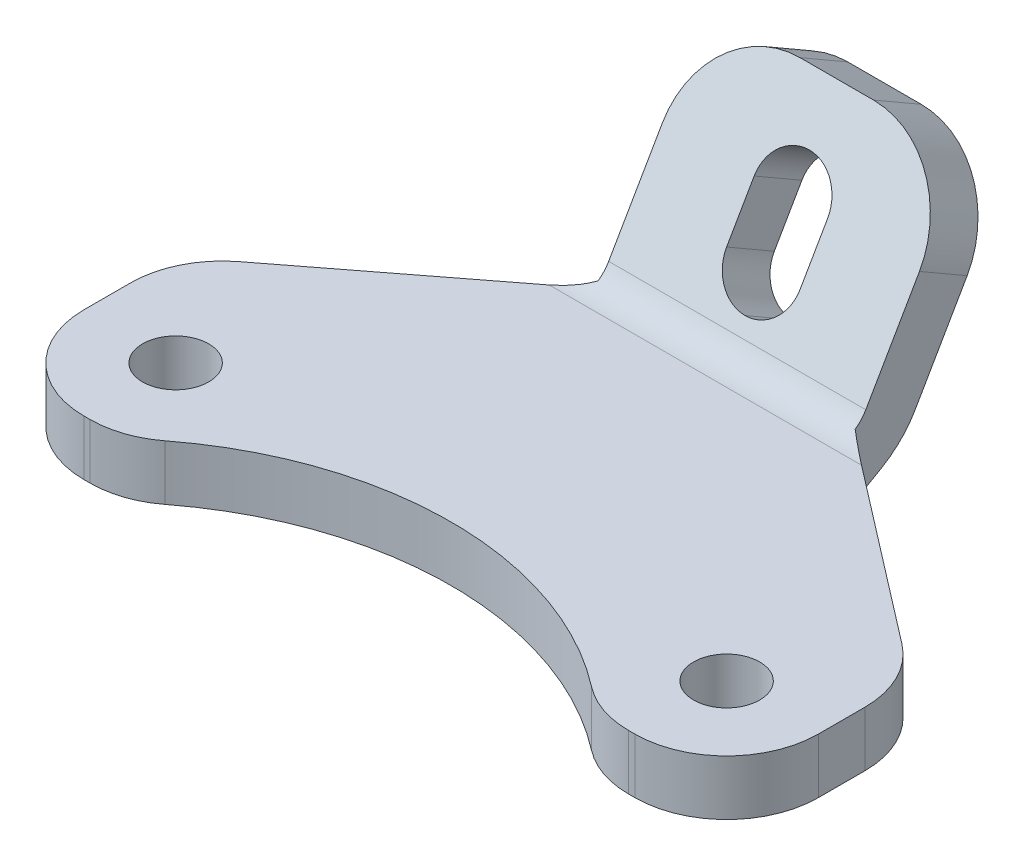
SolidWorks part; units mm, degrees
ref_plane "Front Plane" through (0, 0, 0) normal (0, 0, 1) x (1, 0, 0)
ref_plane "Top Plane" through (0, 0, 0) normal (0, 1, 0) x (1, 0, 0)
ref_plane "Right Plane" through (0, 0, 0) normal (1, 0, 0) x (0, 0, -1)
sketch "Sketch2" plane through (0, 0, 0) normal (0, 1, 0) x (1, 0, 0)
  line L0 (0, 10) -> (13, 20)
  line L1 (0, 0) -> (40, 0)
  line L2 (0, 0) -> (0, 10)
  line L4 (40, 0) -> (40, 10)
  line L5 (13, 20) -> (27, 20)
  line L6 (27, 20) -> (40, 10)
  dimension "D1" = 40
  dimension "D2" = 20
  dimension "D3" = 13
  dimension "D4" = 10
  dimension "D5" = 13
  dimension "D6" = 10
extrude "Boss-Extrude1" add sketch "Sketch2" along normal blind 3
sketch "Sketch3" plane through (0, 3, 0) normal (0, 1, 0) x (1, 0, 0)
  line L0 (0, 0) -> (40, 0) construction
  line L1 (40, 0) -> (40, 10) construction
  circle A0 centre (5, 5) radius 1.8
  circle A1 centre (35, 5) radius 1.8
  dimension "D1" = 3.6
  dimension "D2" = 30
  dimension "D3" = 3.6
  dimension "D4" = 5
  dimension "D6" = 5
  dimension "D5" = 5
extrude "Cut-Extrude1" cut sketch "Sketch3" against normal blind 3
ref_plane "Plane1" through (0, -7.9103, -13.701) normal (0, -0.5, -0.866) x (-1, 0, 0)
sketch "Sketch4" plane through (0, -7.9103, -13.701) normal (0, -0.5, -0.866) x (-1, 0, 0)
  line L1 (-13, 12.5981) -> (-27, 12.5981)
  line L2 (-13, 12.5981) -> (-13, 24.5981)
  line L3 (-13, 24.5981) -> (-27, 24.5981)
  line L4 (-27, 12.5981) -> (-27, 24.5981)
  dimension "D1" = 14
  dimension "D2" = 12
extrude "Boss-Extrude2" add sketch "Sketch4" along normal blind 3 separate body
sketch "Sketch5" plane through (13, 0, 0) normal (-1, 0, 0) x (0, 0, 1)
  line L0 (-22.5981, 1.5) -> (-20, 0)
  line L1 (-20, 0) -> (-20, 3)
  line L2 (-20, 3) -> (-26, 13.3923) construction
  line L3 (-22.5981, 1.5) -> (-20, 3) construction
  line L4 (-20, 3) -> (-22.5981, 1.5)
extrude "Boss-Extrude3" add sketch "Sketch5" against normal blind 14
sketch "Sketch6" plane through (0, -7.9103, -13.701) normal (0, 0.5, 0.866) x (1, 0, 0)
  line L1 (18, 21.5981) -> (22, 21.5981)
  line L2 (18, 21.5981) -> (18, 14.5981)
  line L3 (18, 14.5981) -> (22, 14.5981)
  line L4 (22, 21.5981) -> (22, 14.5981)
  line L5 (13, 24.5981) -> (27, 24.5981) construction
  line L6 (27, 12.5981) -> (13, 12.5981) construction
  line L7 (27, 24.5981) -> (27, 12.5981) construction
  line L8 (13, 12.5981) -> (13, 24.5981) construction
  dimension "D1" = 3
  dimension "D2" = 2
  dimension "D3" = 5
  dimension "D4" = 5
extrude "Cut-Extrude2" cut sketch "Sketch6" against normal blind 3
fillet "Fillet1" radius 2 4 edges at (22, 3.9821, -22.299) (18, 3.9821, -22.299) (18, 10.0442, -25.799) (22, 10.0442, -25.799)
fillet "Fillet2" radius 5 2 edges at (13, 12.6423, -27.299) (27, 12.6423, -27.299)
fillet "Fillet3" radius 5 4 edges at (0, 1.5, -10) (40, 1.5, -10) (40, 1.5, 0) (0, 1.5, 0)
fillet "Fillet4" radius 5 1 edges at (20, 1.5, -22.5981)
sketch "Sketch7" plane through (0, 3, 0) normal (0, 1, 0) x (1, 0, 0)
  line L0 (5, 0) -> (35, 0) construction
  line L2 (40, 5) -> (40, 7.538) construction
  circle A0 centre (20, -14) radius 19
  dimension "D1" = 38
  dimension "D2" = 14
  dimension "D3" = 20
extrude "Cut-Extrude3" cut sketch "Sketch7" against normal blind 3
fillet "Fillet5" radius 5 2 edges at (32.8452, 1.5, 0) (7.1548, 1.5, 0)
fillet "Fillet7" radius 2 1 edges at (20, 3, -20)
